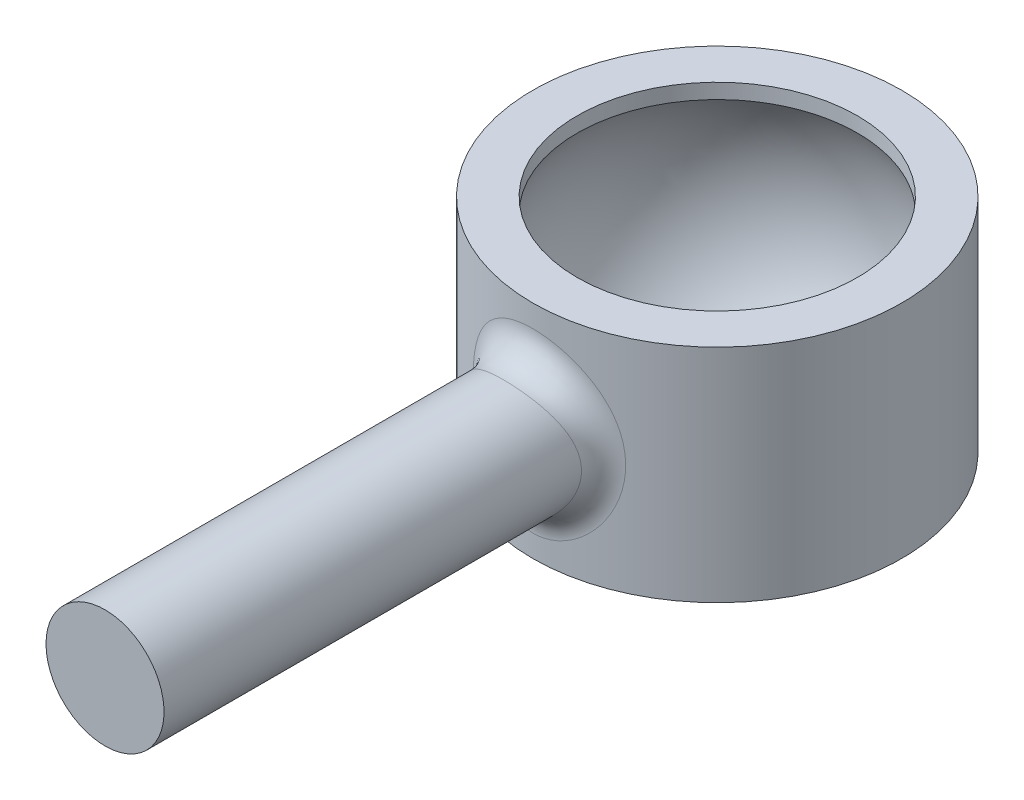
SolidWorks part; units mm, degrees
ref_plane "Front Plane" through (0, 0, 0) normal (0, 0, 1) x (1, 0, 0)
ref_plane "Top Plane" through (0, 0, 0) normal (0, 1, 0) x (1, 0, 0)
ref_plane "Right Plane" through (0, 0, 0) normal (1, 0, 0) x (0, 0, -1)
sketch "Sketch1" plane through (0, 0, 0) normal (0, 1, 0) x (1, 0, 0)
  circle A0 centre (0, 0) radius 12.5
  circle A1 centre (0, 0) radius 9.5
  dimension "D1" = 3
  dimension "D2" = 25
extrude "Boss-Extrude1" add sketch "Sketch1" along normal mid plane 15
sketch "Sketch3" plane through (0, 0, 0) normal (0, 1, 0) x (1, 0, 0)
  line L0 (0, -11.5) -> (0, 11.5)
  arc A0 (0, 11.5) -> (0, -11.5) centre (0, 0) ccw
  point P5 (0, 0)
  dimension "D1" = 23
revolve "Cut-Revolve1" cut sketch "Sketch3" angle 360 about L0
sketch "Sketch4" plane through (0, 0, 0) normal (0, 1, 0) x (1, 0, 0)
  line L0 (0, -11.5) -> (-4, -11.5)
  line L1 (-4, -11.5) -> (-4, -41.5)
  line L2 (0, -11.5) -> (0, -41.5)
  line L3 (0, -41.5) -> (-4, -41.5)
  circle A0 centre (0, 0) radius 11.5 construction
  dimension "D1" = 4
  dimension "D2" = 30
revolve "Revolve1" add sketch "Sketch4" angle 360 about L2
fillet "Fillet1" radius 2 1 edges at (3.9381, -0.7011, 11.8635)
